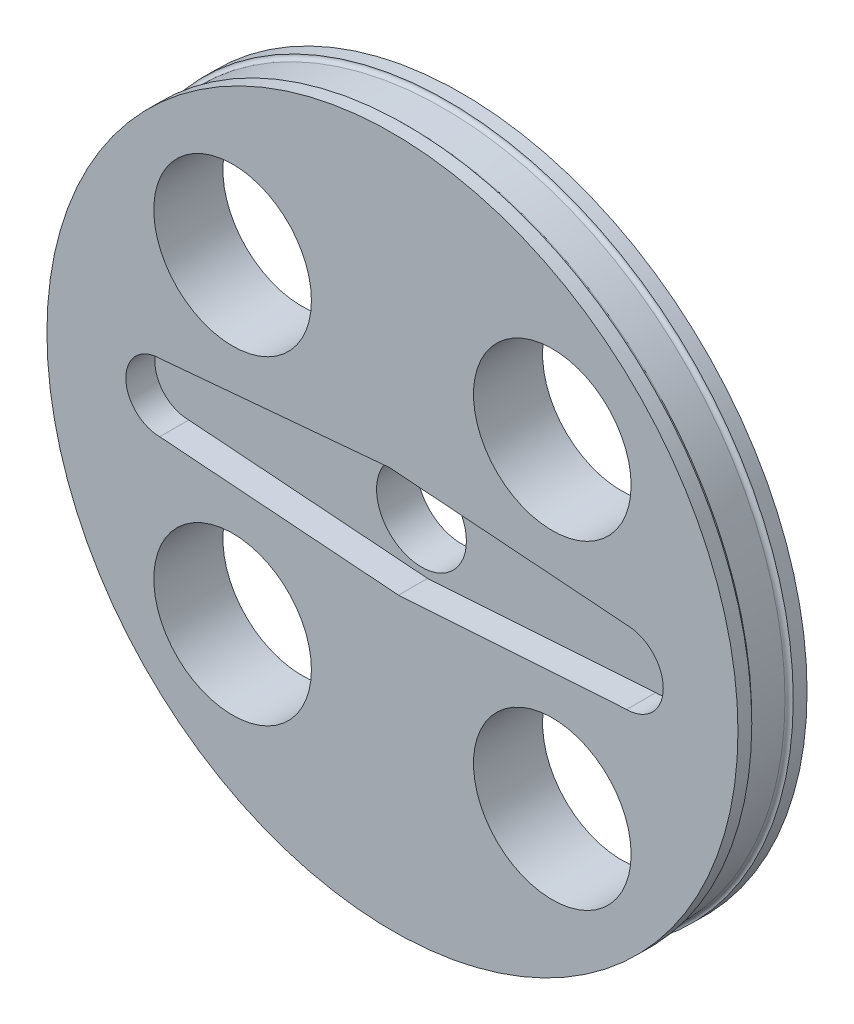
SolidWorks part; units mm, degrees
ref_plane "Front Plane" through (0, 0, 0) normal (0, 0, 1) x (1, 0, 0)
ref_plane "Top Plane" through (0, 0, 0) normal (0, 1, 0) x (1, 0, 0)
ref_plane "Right Plane" through (0, 0, 0) normal (1, 0, 0) x (0, 0, -1)
sketch "Sketch1" plane through (0, 0, 0) normal (0, 0, 1) x (1, 0, 0)
  circle A0 centre (-38.3081, 20.9098) radius 25
  dimension "D1" = 50
extrude "Boss-Extrude1" add sketch "Sketch1" along normal blind 5
sketch "Sketch9" plane through (0, 0, 0) normal (0, 0, -1) x (-1, 0, 0)
  point P0 (38.3081, 20.9098)
ref_axis "Axis3" through (-38.3081, 20.9098, 0) along (0, 0, 1)
sketch "Sketch10" plane through (0, 0, 5) normal (0, 0, 1) x (1, 0, 0)
  circle A0 centre (-38.3081, 20.9098) radius 25 construction
  point P0 (-38.3081, 45.9098)
ref_plane "Plane1" through (-38.3081, 0, 0) normal (-1, 0, 0) x (0, 0, 1)
sketch "Sketch12" plane through (-38.3081, 0, 0) normal (-1, 0, 0) x (0, 0, 1)
  line L0 (2.5, 45.9098) -> (4, 45.9098)
  line L1 (5, 45.9098) -> (0, 45.9098) construction
  line L2 (2.5, 45.9098) -> (1, 45.9098)
  line L3 (1, 45.9098) -> (1, 45.6098)
  line L4 (1, 45.6098) -> (2.5, 45.6098)
  line L5 (4, 45.9098) -> (4, 45.6098)
  line L6 (4, 45.6098) -> (2.5, 45.6098)
  dimension "D1" = 1.5
  dimension "D2" = 1.5
  dimension "D3" = 0.3
revolve "Cut-Revolve1" cut sketch "Sketch12" angle 360 about axis through (-38.3081, 20.9098, 0) along (0, 0, 1)
fillet "Fillet1" radius 0.3 2 edges at (-63.0081, 20.9098, 4) (-63.0081, 20.9098, 1)
sketch "Sketch13" plane through (0, 0, 5) normal (0, 0, 1) x (1, 0, 0)
  line L0 (-55.1454, 20.9098) -> (-21.3636, 20.9098) construction
  line L2 (-38.5378, 24.8394) -> (-55.1454, 23.3637)
  line L3 (-37.8672, 17.1687) -> (-55.1454, 18.456)
  line L4 (-38.5378, 24.8394) -> (-21.3636, 23.5598)
  line L5 (-37.8672, 17.1687) -> (-21.3636, 18.2598)
  arc A0 (-21.3636, 18.2598) -> (-21.3636, 23.5598) centre (-21.3636, 20.9098) ccw
  arc A1 (-55.1454, 18.456) -> (-55.1454, 23.3637) centre (-55.1454, 20.9098) cw
  point P2 (-38.3081, 20.9098)
  point P7 (-38.3081, 20.9098)
  dimension "D3" = 5.3
  dimension "D2" = 7.7
extrude "Cut-Extrude1" cut sketch "Sketch13" against normal blind 2.1
sketch "Sketch15" plane through (0, 0, 2.9) normal (0, 0, 1) x (1, 0, 0)
  circle A0 centre (-38.3081, 20.9098) radius 3.25
  dimension "D1" = 6.5
extrude "Cut-Extrude2" cut sketch "Sketch15" against normal blind 10.1
sketch "Sketch18" plane through (0, 0, 5) normal (0, 0, 1) x (1, 0, 0)
  line L1 (-63.3081, 20.9098) -> (-13.3081, 20.9098) construction
  circle A0 centre (-26.7426, 32.4753) radius 5.7024
  circle A1 centre (-38.3081, 20.9098) radius 25 construction
  circle A2 centre (-26.7426, 9.3443) radius 5.7024
  circle A3 centre (-49.8736, 9.3443) radius 5.7024
  circle A4 centre (-49.8736, 32.4753) radius 5.7024
  dimension "D2" = 4
extrude "Cut-Extrude4" cut sketch "Sketch18" against normal blind 10.1
